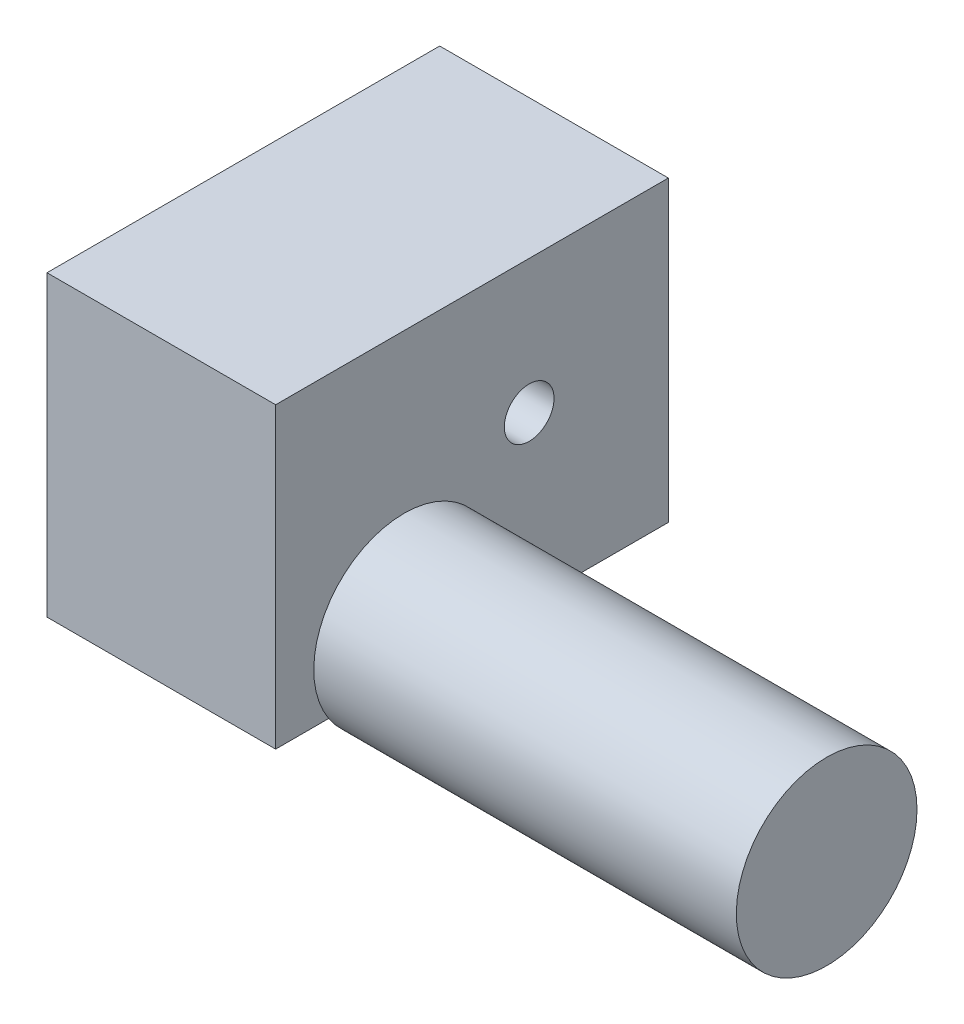
SolidWorks part; units mm, degrees
ref_plane "Front Plane" through (0, 0, 0) normal (1, 0, 0) x (0, 1, 0)
ref_plane "Top Plane" through (0, 0, 0) normal (0, 0, 1) x (0, 1, 0)
ref_plane "Right Plane" through (0, 0, 0) normal (0, 1, 0) x (-1, 0, 0)
sketch "Sketch1" plane through (0, 0, 0) normal (1, 0, 0) x (0, 1, 0)
  line L1 (0, 0) -> (120, 0)
  line L2 (0, 0) -> (0, -158)
  line L3 (0, -158) -> (120, -158)
  line L4 (120, 0) -> (120, -158)
  dimension "D1" = 158
  dimension "D2" = 120
extrude "Boss-Extrude1" add sketch "Sketch1" along normal blind 92
sketch "Sketch2" plane through (92, 0, 0) normal (1, 0, 0) x (0, 1, 0)
  line L1 (120, 0) -> (0, 0) construction
  line L2 (120, -53.0385) -> (136.8, -53.0385)
  line L3 (120, -158) -> (120, 0) construction
  line L4 (100.0099, -15.3398) -> (100.0099, 0)
  circle A0 centre (100.0099, -51.6898) radius 36.35
  dimension "D3" = 72.7
  dimension "D2" = 16.8
extrude "Boss-Extrude2" add sketch "Sketch2" along normal blind 170 contours A0
mirror "Mirror1" about plane through (0, 0, 0) normal (0, 1, 0) of bodies 102
sketch "Sketch4" plane through (0, 120, 0) normal (0, 1, 0) x (-1, 0, 0)
  line L1 (-389.2335, -264.3158) -> (265.7401, -264.3158)
  line L2 (-389.2335, -264.3158) -> (-389.2335, 163.9896)
  line L3 (-389.2335, 163.9896) -> (265.7401, 163.9896)
  line L4 (265.7401, -264.3158) -> (265.7401, 163.9896)
extrude "Cut-Extrude1" cut sketch "Sketch4" against normal up to surface (120 mm away) and the other way through all up to plane "Right Plane"
sketch "Sketch5" plane through (92, 0, 0) normal (1, 0, 0) x (0, 1, 0)
  line L0 (0, -158) -> (-45, -158)
  line L2 (-120, -158) -> (0, -158) construction
  line L5 (-120, -158) -> (-62.5, -158)
  line L6 (-62.5, -158) -> (-45, -158)
  line L7 (-53.75, -158) -> (-53.75, -112)
  circle A3 centre (-53.75, -102) radius 10
  dimension "D3" = 57.5
  dimension "D1" = 20
  dimension "D2" = 45
  dimension "D4" = 46
extrude "Cut-Extrude2" cut sketch "Sketch5" against normal through all contours A3
